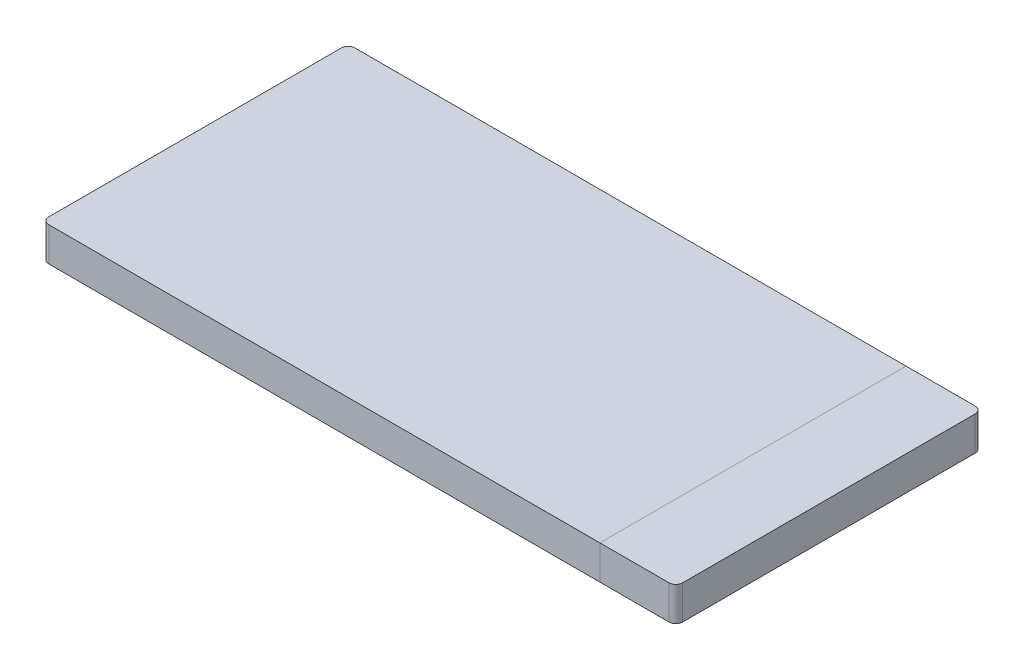
SolidWorks part; units mm, degrees
ref_plane "Front Plane" through (0, 0, 0) normal (0, 0, 1) x (1, 0, 0)
ref_plane "Top Plane" through (0, 0, 0) normal (0, 1, 0) x (1, 0, 0)
ref_plane "Right Plane" through (0, 0, 0) normal (1, 0, 0) x (0, 0, -1)
sketch "草图1" plane through (0, 0, 0) normal (0, 1, 0) x (1, 0, 0)
  line L1 (-13.975, 6.75) -> (13.975, 6.75)
  line L2 (-13.975, 6.75) -> (-13.975, -6.75)
  line L3 (-13.975, -6.75) -> (13.975, -6.75)
  line L4 (13.975, 6.75) -> (13.975, -6.75)
  line L5 (10.625, 6.75) -> (13.975, 6.75)
  line L6 (10.625, 6.75) -> (10.625, -6.75)
  line L7 (10.625, -6.75) -> (13.975, -6.75)
  line L8 (13.975, 6.75) -> (13.975, -6.75)
  point P4 (-13.975, 0)
  point P6 (0, 6.75)
  dimension "D1" = 27.95
  dimension "D2" = 13.5
  dimension "D3" = 3.35
extrude "凸台-拉伸1" add sketch "草图1" along normal blind 1.5 contours L6 L1 L2 L3 region at (-1.675, 0, 0)
extrude "凸台-拉伸2" add sketch "草图1<3>" along normal blind 1.5 separate body contours L1 L6 L3 L4 region at (12.3, 0, 0)
sketch "草图1<3>" plane through (0, 0, 0) normal (0, 1, 0) x (1, 0, 0) same geometry as "草图1"
fillet "圆角1" radius 0.3 2 edges at (13.975, 0.75, -6.75) (13.975, 0.75, 6.75)
fillet "圆角2" radius 0.3 2 edges at (-13.975, 0.75, -6.75) (-13.975, 0.75, 6.75)
